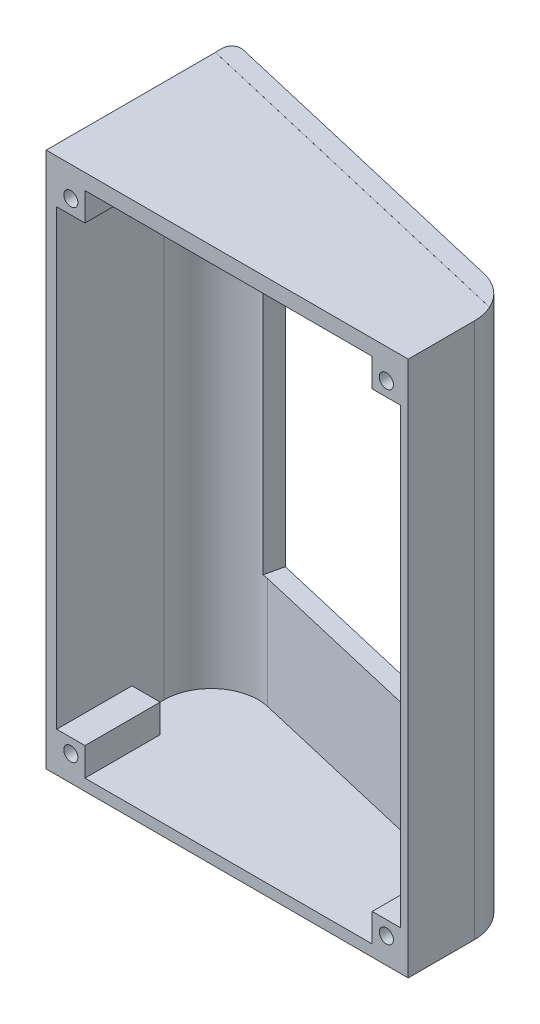
SolidWorks part; units mm, degrees
ref_plane "Plano frontal" through (0, 0, 0) normal (0, 0, 1) x (1, 0, 0)
ref_plane "Plano superior" through (0, 0, 0) normal (0, 1, 0) x (1, 0, 0)
ref_plane "Plano direito" through (0, 0, 0) normal (1, 0, 0) x (0, 0, -1)
sketch "Esboço1" plane through (0, 0, 0) normal (0, 1, 0) x (1, 0, 0)
  line L0 (113.2967, 18.3929) -> (190.2967, 0.3929)
  line L1 (190.2967, -21.6071) -> (113.2967, -21.6071)
  line L2 (190.2967, -21.6071) -> (190.2967, 0.3929)
  line L4 (113.2967, -21.6071) -> (113.2967, 18.3929)
  dimension "D1" = 40
  dimension "D2" = 77
  dimension "D3" = 22
extrude "Ressalto-extrusão1" add sketch "Esboço1" along normal blind 114
sketch3d "3DSketch1"
  line L0 (113.2967, 114, 21.6071) -> (190.6756, -0.5609, 21.6071) construction
  line L2 (115.5373, 110.6828, 21.6071) -> (188.6493, 110.6828, 21.6071)
  line L3 (115.5373, 110.6828, 21.6071) -> (115.5373, 2.4391, 21.6071)
  line L4 (115.5373, 2.4391, 21.6071) -> (188.6493, 2.4391, 21.6071)
  line L5 (188.6493, 110.6828, 21.6071) -> (188.6493, 2.4391, 21.6071)
  line L7 (190.6756, -0.5609, 21.6071) -> (191.6493, 113.4391, 21.6071) construction
  line L8 (191.6493, 113.4391, 21.6071) -> (112.5373, -0.5609, 21.6071) construction
  dimension "D1" = 21.6071
  dimension "D2" = 3.3172
  dimension "D3" = 3
  dimension "D4" = 3
  dimension "D5" = 3
extrude "Corte-extrusão1" cut sketch "3DSketch1" along direction (0, 0, -1) on the side of the normal blind 59
sketch3d "3DSketch3"
  line L3 (190.2967, 114, -0.3929) -> (190.2967, 0, -0.3929) construction
  line L4 (113.2967, 114, -18.3929) -> (113.2967, 0, -18.3929) construction
  line L6 (113.2807, 114.0176, -18.3966) -> (190.2807, 114.0176, -0.3966)
  line L7 (113.2807, 114.0176, -18.3966) -> (113.2807, -0.0013, -18.3966)
  line L8 (113.2807, -0.0013, -18.3966) -> (190.2807, -0.0013, -0.3966)
  line L9 (190.2807, 114.0176, -0.3966) -> (190.2807, -0.0013, -0.3966)
extrude "Ressalto-extrusão3" add sketch "3DSketch3" along direction (0, 0, -1) on the side of the normal blind 4
fillet "Filete1" radius 10 1 edges at (190.2967, 57, -0.3929)
fillet "Filete2" radius 10 1 edges at (188.6493, 56.5609, 3.222)
fillet "Filete3" radius 10 1 edges at (115.5373, 56.5609, -13.8691)
fillet "Filete4" radius 2 1 edges
sketch3d "3DSketch4"
  line L0 (182.573, 114.0176, -2.1984) -> (182.573, -0.0013, -2.1984) construction
  line L1 (182.573, 114.0176, -2.1984) -> (115.736, 114.0176, -17.8226) construction
  line L2 (115.736, 114.0176, -17.8226) -> (182.573, -0.0013, -2.1984) construction
  line L3 (115.736, -0.0013, -17.8226) -> (115.736, 114.0176, -17.8226) construction
  line L4 (182.573, -0.0013, -2.1984) -> (182.573, 114.0176, -2.1984) construction
  line L5 (182.573, 114.0176, -2.1984) -> (115.736, -0.0013, -17.8226) construction
  line L6 (170.8204, 88.0082, -4.9458) -> (127.4886, 88.0082, -15.0753)
  line L7 (170.8204, 88.0082, -4.9458) -> (170.8204, 26.0082, -4.9458)
  line L8 (170.8204, 26.0082, -4.9458) -> (127.4886, 26.0082, -15.0753)
  line L9 (127.4886, 88.0082, -15.0753) -> (127.4886, 26.0082, -15.0753)
  line L10 (149.1545, 57.0082, -10.0105) -> (115.736, 57.0082, -17.8226) construction
  line L11 (115.736, 57.0082, -17.8226) -> (182.573, 57.0082, -2.1984) construction
  dimension "D1" = 62
  dimension "D2" = 44.5
  dimension "D3" = 31
  dimension "D4" = 22.25
extrude "Corte-extrusão2" cut sketch "3DSketch4" along direction (-0.2276, 0, 0.9737) on the side of the normal blind 19 and the other way blind 10
sketch3d "3DSketch5"
  line L0 (121.5373, 104.6828, 21.6071) -> (115.5373, 110.6828, 21.6071) construction
  line L1 (115.5373, 110.6828, 21.6071) -> (121.5373, 110.6828, 21.6071)
  line L2 (115.5373, 110.6828, 21.6071) -> (115.5373, 104.6828, 21.6071)
  line L3 (115.5373, 104.6828, 21.6071) -> (121.5373, 104.6828, 21.6071)
  line L4 (121.5373, 110.6828, 21.6071) -> (121.5373, 104.6828, 21.6071)
  line L5 (188.6493, 110.6828, 21.6071) -> (182.6493, 110.6828, 21.6071)
  line L6 (188.6493, 110.6828, 21.6071) -> (188.6493, 104.6828, 21.6071)
  line L7 (188.6493, 104.6828, 21.6071) -> (182.6493, 104.6828, 21.6071)
  line L8 (182.6493, 110.6828, 21.6071) -> (182.6493, 104.6828, 21.6071)
  line L9 (188.6493, 2.4391, 21.6071) -> (182.6493, 2.4391, 21.6071)
  line L10 (188.6493, 2.4391, 21.6071) -> (188.6493, 8.4391, 21.6071)
  line L11 (188.6493, 8.4391, 21.6071) -> (182.6493, 8.4391, 21.6071)
  line L12 (182.6493, 2.4391, 21.6071) -> (182.6493, 8.4391, 21.6071)
  line L13 (115.5373, 2.4391, 21.6071) -> (121.5373, 2.4391, 21.6071)
  line L14 (115.5373, 2.4391, 21.6071) -> (115.5373, 8.4391, 21.6071)
  line L15 (115.5373, 8.4391, 21.6071) -> (121.5373, 8.4391, 21.6071)
  line L16 (121.5373, 2.4391, 21.6071) -> (121.5373, 8.4391, 21.6071)
  line L17 (121.5373, 110.6828, 21.6071) -> (115.5373, 104.6828, 21.6071) construction
  line L18 (182.6493, 110.6828, 21.6071) -> (188.6493, 104.6828, 21.6071) construction
  line L19 (182.6493, 104.6828, 21.6071) -> (188.6493, 110.6828, 21.6071) construction
  line L20 (182.6493, 8.4391, 21.6071) -> (188.6493, 2.4391, 21.6071) construction
  line L21 (188.6493, 8.4391, 21.6071) -> (182.6493, 2.4391, 21.6071) construction
  line L22 (121.5373, 8.4391, 21.6071) -> (115.5373, 2.4391, 21.6071) construction
  line L23 (121.5373, 2.4391, 21.6071) -> (115.5373, 8.4391, 21.6071) construction
  circle A0 centre (118.5373, 107.6828, 21.6071) radius 1.5
  circle A1 centre (185.6493, 107.6828, 21.6071) radius 1.5
  circle A2 centre (185.6493, 5.4391, 21.6071) radius 1.5
  circle A3 centre (118.5373, 5.4391, 21.6071) radius 1.5
  point P23 (118.5373, 107.6828, 23.1071)
  point P26 (185.6493, 107.6828, 23.1071)
  point P29 (185.6493, 5.4391, 23.1071)
  point P32 (118.5373, 5.4391, 23.1071)
  dimension "D1" = 3
  dimension "D2" = 3
  dimension "D3" = 3
  dimension "D4" = 3
  dimension "D5" = 6
  dimension "D6" = 6
  dimension "D7" = 6
  dimension "D8" = 6
  dimension "D9" = 6
  dimension "D10" = 6
  dimension "D11" = 6
  dimension "D12" = 6
extrude "Ressalto-extrusão6" add sketch "3DSketch5" along direction (0, 0, -1) on the side of the normal blind 16
